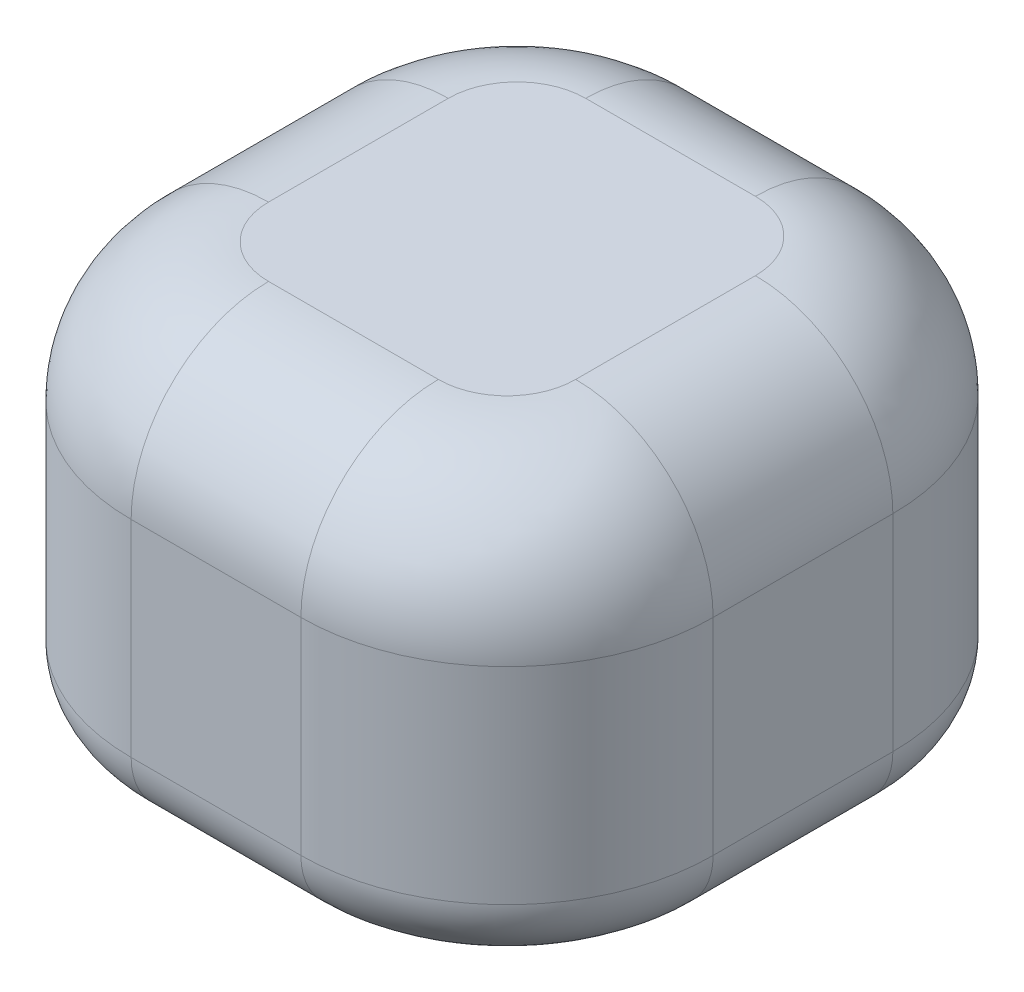
SolidWorks part; units mm, degrees
ref_plane "Front Plane" through (0, 0, 0) normal (0, 0, 1) x (1, 0, 0)
ref_plane "Top Plane" through (0, 0, 0) normal (0, 1, 0) x (1, 0, 0)
ref_plane "Right Plane" through (0, 0, 0) normal (1, 0, 0) x (0, 0, -1)
sketch "Sketch1" plane through (0, 0, 0) normal (0, 1, 0) x (1, 0, 0)
  line L0 (-96.2108, -81.7523) -> (106.8591, 64.0647) construction
  line L1 (-42.3542, -43.0799) -> (42.3542, -43.0799)
  line L2 (-42.3542, -43.0799) -> (-42.3542, 43.0799)
  line L3 (-42.3542, 43.0799) -> (42.3542, 43.0799)
  line L4 (42.3542, -43.0799) -> (42.3542, 43.0799)
  line L5 (-42.3542, -43.0799) -> (42.3542, 43.0799) construction
  line L6 (-42.3542, 43.0799) -> (42.3542, -43.0799) construction
  point P0 (0, 0)
  point P6 (32.8332, 32.2237)
  point P7 (-34.2214, -32.4199)
  point P10 (-46.6306, 37.112)
extrude "Boss-Extrude1" add sketch "Sketch1" along normal blind 30 and the other way blind 30
fillet "Fillet1" radius 30 4 edges at (42.3542, 0, 43.0799) (42.3542, 0, -43.0799) (-42.3542, 0, 43.0799) (-42.3542, 0, -43.0799)
fillet "Fillet2" radius 20 8 edges at (-33.5674, 30, 34.2931) (-42.3542, 30, 0) (-33.5674, 30, -34.2931) (0, 30, -43.0799) (33.5674, 30, -34.2931) (42.3542, 30, 0) (33.5674, 30, 34.2931) (0, 30, 43.0799)
fillet "Fillet3" radius 10 8 edges at (33.5674, -30, -34.2931) (0, -30, -43.0799) (-33.5674, -30, -34.2931) (-42.3542, -30, 0) (-33.5674, -30, 34.2931) (0, -30, 43.0799) (33.5674, -30, 34.2931) (42.3542, -30, 0)
